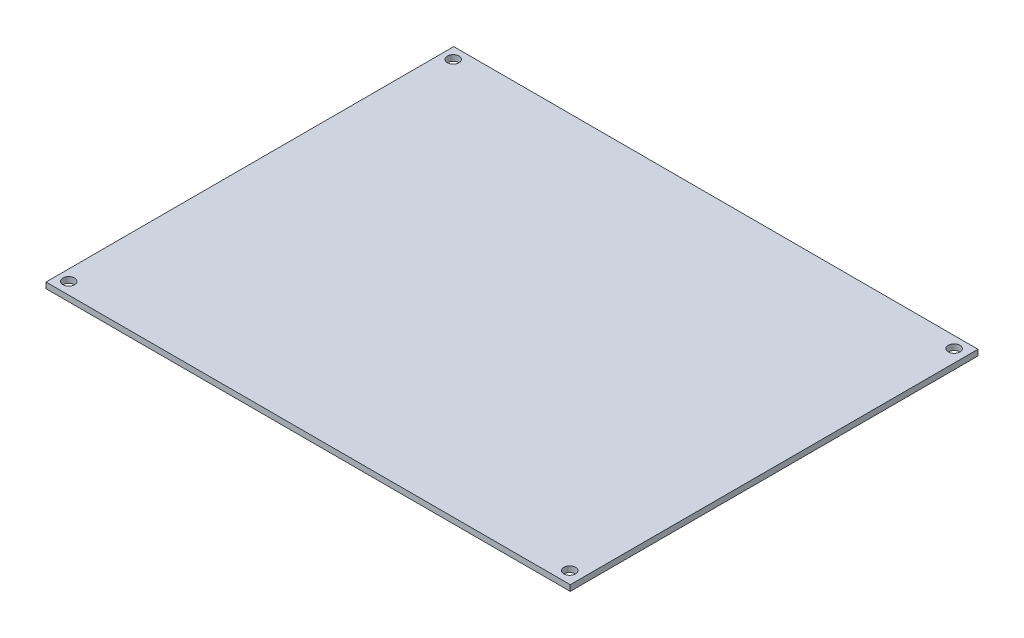
SolidWorks part; units mm, degrees
ref_plane "Front Plane" through (0, 0, 0) normal (0, 0, 1) x (1, 0, 0)
ref_plane "Top Plane" through (0, 0, 0) normal (0, 1, 0) x (1, 0, 0)
ref_plane "Right Plane" through (0, 0, 0) normal (1, 0, 0) x (0, 0, -1)
sketch "Sketch1" plane through (0, 0, 0) normal (0, 1, 0) x (1, 0, 0)
  line L1 (0, 0) -> (90, 0)
  line L2 (0, 0) -> (0, 70)
  line L3 (0, 70) -> (90, 70)
  line L4 (90, 0) -> (90, 70)
  dimension "D1" = 90
  dimension "D2" = 70
extrude "Boss-Extrude1" add sketch "Sketch1" along normal blind 1
sketch "Sketch2" plane through (0, 1, 0) normal (0, 1, 0) x (1, 0, 0)
  line L0 (0, 70) -> (90, 0) construction
  line L2 (1.8522, 2.05) -> (87.8522, 2.05) construction
  line L3 (1.8522, 2.05) -> (1.8522, 68.05) construction
  line L4 (1.8522, 68.05) -> (87.8522, 68.05) construction
  line L5 (87.8522, 2.05) -> (87.8522, 68.05) construction
  line L6 (1.8522, 2.05) -> (87.8522, 68.05) construction
  line L7 (1.8522, 68.05) -> (87.8522, 2.05) construction
  circle A0 centre (87.8522, 68.05) radius 1
  circle A1 centre (87.8522, 2.05) radius 1
  circle A2 centre (1.8522, 2.05) radius 1
  circle A3 centre (1.8522, 68.05) radius 1
  point P4 (44.8522, 35.05)
  dimension "D1" = 2
  dimension "D2" = 66
  dimension "D3" = 86
extrude "Cut-Extrude1" cut sketch "Sketch2" against normal blind 10
